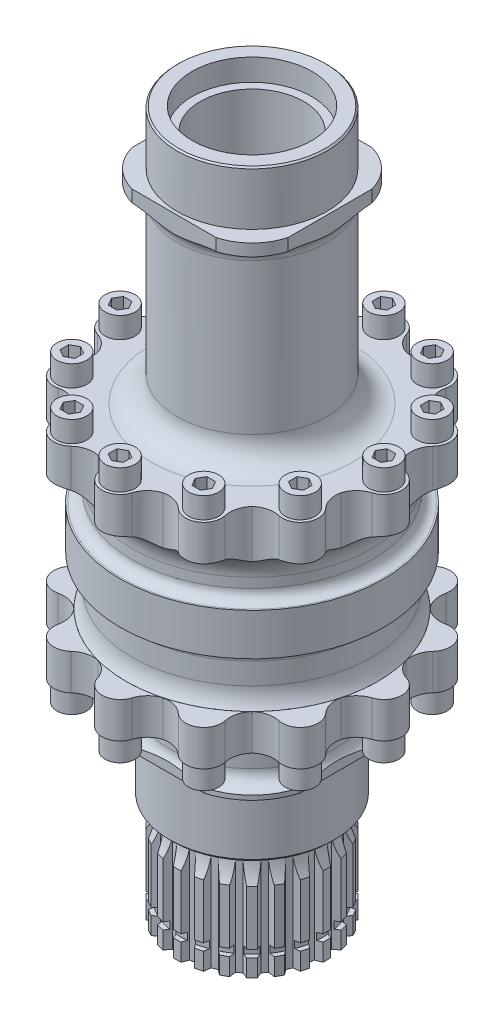
SolidWorks part; units mm, degrees
ref_plane "Front Plane" through (0, 0, 0) normal (0, 0, 1) x (1, 0, 0)
ref_plane "Top Plane" through (0, 0, 0) normal (0, 1, 0) x (1, 0, 0)
ref_plane "Right Plane" through (0, 0, 0) normal (1, 0, 0) x (0, 0, -1)
sketch "Sketch1" plane through (0, 0, 0) normal (0, 1, 0) x (1, 0, 0)
  circle A0 centre (0, 0) radius 44
  dimension "D1" = 88
extrude "Boss-Extrude1" add sketch "Sketch1" along normal mid plane 14
ref_plane "Plane1" through (0, 35.625, 0) normal (0, 1, 0) x (1, 0, 0)
sketch "Sketch2" plane through (0, 35.625, 0) normal (0, 1, 0) x (1, 0, 0)
  circle A0 centre (0, 0) radius 40
  dimension "D1" = 80
extrude "Boss-Extrude2" add sketch "Sketch2" against normal up to surface (42.625 mm away)
sketch "Sketch3" plane through (0, 35.625, 0) normal (0, 1, 0) x (1, 0, 0)
  circle A0 centre (0, 0) radius 42
  dimension "D1" = 84
extrude "Boss-Extrude3" add sketch "Sketch3" against normal blind 12
sketch "Sketch4" plane through (0, 35.625, 0) normal (0, 1, 0) x (1, 0, 0)
  line L0 (-11.2231, 40.4727) -> (11.2231, 40.4727)
  arc A1 (5.7261, 45.7922) -> (-5.7261, 45.7922) centre (0, 44) ccw
  circle A2 centre (0, 0) radius 42
  circle A3 centre (0, 0) radius 42
  arc A4 (-11.2231, 40.4727) -> (-5.7261, 45.7922) centre (-13.3609, 48.1818) ccw
  arc A5 (5.7261, 45.7922) -> (11.2231, 40.4727) centre (13.3609, 48.1818) ccw
  dimension "D2" = 12
  dimension "D4" = 16
  dimension "D5" = 16
  dimension "D3" = 44
  dimension "D1" = 0
extrude "Boss-Extrude4" add sketch "Sketch4" against normal up to surface (59.25 mm away) contours A1 A4 L0 A5
pattern_circular "CirPattern1" count 12 over 360 about axis through (0, 0, 0) along (0, 1, 0) of "Boss-Extrude4"
sketch "Sketch6" plane through (0, 35.625, 0) normal (0, 1, 0) x (1, 0, 0)
  circle A0 centre (0, 44) radius 5
  arc A1 (5.7261, 45.7922) -> (-5.7261, 45.7922) centre (0, 44) ccw construction
  dimension "D1" = 10
extrude "Boss-Extrude5" add sketch "Sketch6" along normal blind 7 separate body
sketch "Sketch7" plane through (0, 42.625, 0) normal (0, 1, 0) x (1, 0, 0)
  line L1 (2.5, 45.4434) -> (0, 46.8868)
  line L2 (0, 46.8868) -> (-2.5, 45.4434)
  line L3 (-2.5, 45.4434) -> (-2.5, 42.5566)
  line L4 (-2.5, 42.5566) -> (0, 41.1132)
  line L5 (0, 41.1132) -> (2.5, 42.5566)
  line L6 (2.5, 42.5566) -> (2.5, 45.4434)
  circle A0 centre (0, 44) radius 2.5 construction
  dimension "D1" = 5
extrude "Cut-Extrude1" cut sketch "Sketch7" against normal blind 4.5
pattern_circular "CirPattern5" count 12 over 360 about axis through (0, 0, 0) along (0, 1, 0) of bodies 118
mirror "Mirror2" about plane through (0, 0, 0) normal (0, 1, 0) of "Boss-Extrude2"
mirror "Mirror3" about plane through (0, 0, 0) normal (0, 1, 0) of "Boss-Extrude3"
sketch "Sketch8" plane through (0, -35.625, 0) normal (0, -1, 0) x (1, 0, 0)
  line L0 (40.5785, 10.873) -> (40.5785, -10.873)
  line L1 (40.5785, -10.873) -> (29.7055, -29.7055)
  line L2 (29.7055, -29.7055) -> (10.873, -40.5785)
  line L3 (10.873, -40.5785) -> (-10.873, -40.5785)
  line L4 (-10.873, -40.5785) -> (-29.7055, -29.7055)
  line L5 (-29.7055, -29.7055) -> (-40.5785, -10.873)
  line L6 (-40.5785, -10.873) -> (-40.5785, 10.873)
  line L7 (-40.5785, 10.873) -> (-29.7055, 29.7055)
  line L8 (-29.7055, 29.7055) -> (-10.873, 40.5785)
  line L9 (-10.873, 40.5785) -> (10.873, 40.5785)
  line L10 (10.873, 40.5785) -> (29.7055, 29.7055)
  line L11 (29.7055, 29.7055) -> (40.5785, 10.873)
  circle A2 centre (0, 0) radius 42
  circle A3 centre (0, 0) radius 42
  arc A10 (40.5785, -10.873) -> (42.5203, -17.9372) centre (48.4071, -12.5201) ccw
  arc A11 (36.7942, -27.855) -> (42.5203, -17.9372) centre (38.1051, -22) ccw
  arc A12 (36.7942, -27.855) -> (29.7055, -29.7055) centre (35.0463, -35.6617) ccw
  arc A13 (45.7922, -5.7261) -> (40.5785, -10.873) centre (48.1818, -13.3609) ccw
  arc A14 (40.5785, 10.873) -> (45.7922, 5.7261) centre (48.1818, 13.3609) ccw
  arc A15 (45.7922, -5.7261) -> (45.7922, 5.7261) centre (44, 0) ccw
  arc A16 (45.7922, -5.7261) -> (40.5785, -10.873) centre (48.1818, -13.3609) ccw
  arc A17 (40.5785, 10.873) -> (45.7922, 5.7261) centre (48.1818, 13.3609) ccw
  arc A18 (45.7922, -5.7261) -> (45.7922, 5.7261) centre (44, 0) ccw
  arc A19 (29.7055, -29.7055) -> (27.855, -36.7942) centre (35.6617, -35.0463) ccw
  arc A20 (17.9372, -42.5203) -> (27.855, -36.7942) centre (22, -38.1051) ccw
  arc A21 (17.9372, -42.5203) -> (10.873, -40.5785) centre (12.5201, -48.4071) ccw
  arc A22 (10.873, -40.5785) -> (5.7261, -45.7922) centre (13.3609, -48.1818) ccw
  arc A23 (-5.7261, -45.7922) -> (5.7261, -45.7922) centre (0, -44) ccw
  arc A24 (-5.7261, -45.7922) -> (-10.873, -40.5785) centre (-13.3609, -48.1818) ccw
  arc A25 (-10.873, -40.5785) -> (-17.9372, -42.5203) centre (-12.5201, -48.4071) ccw
  arc A26 (-27.855, -36.7942) -> (-17.9372, -42.5203) centre (-22, -38.1051) ccw
  arc A27 (-27.855, -36.7942) -> (-29.7055, -29.7055) centre (-35.6617, -35.0463) ccw
  arc A28 (-29.7055, -29.7055) -> (-36.7942, -27.855) centre (-35.0463, -35.6617) ccw
  arc A29 (-42.5203, -17.9372) -> (-36.7942, -27.855) centre (-38.1051, -22) ccw
  arc A30 (-42.5203, -17.9372) -> (-40.5785, -10.873) centre (-48.4071, -12.5201) ccw
  arc A31 (-40.5785, -10.873) -> (-45.7922, -5.7261) centre (-48.1818, -13.3609) ccw
  arc A32 (-45.7922, 5.7261) -> (-45.7922, -5.7261) centre (-44, 0) ccw
  arc A33 (-45.7922, 5.7261) -> (-40.5785, 10.873) centre (-48.1818, 13.3609) ccw
  arc A34 (-40.5785, 10.873) -> (-42.5203, 17.9372) centre (-48.4071, 12.5201) ccw
  arc A35 (-36.7942, 27.855) -> (-42.5203, 17.9372) centre (-38.1051, 22) ccw
  arc A36 (-36.7942, 27.855) -> (-29.7055, 29.7055) centre (-35.0463, 35.6617) ccw
  arc A37 (-29.7055, 29.7055) -> (-27.855, 36.7942) centre (-35.6617, 35.0463) ccw
  arc A38 (-17.9372, 42.5203) -> (-27.855, 36.7942) centre (-22, 38.1051) ccw
  arc A39 (-17.9372, 42.5203) -> (-10.873, 40.5785) centre (-12.5201, 48.4071) ccw
  arc A40 (-10.873, 40.5785) -> (-5.7261, 45.7922) centre (-13.3609, 48.1818) ccw
  arc A41 (5.7261, 45.7922) -> (-5.7261, 45.7922) centre (0, 44) ccw
  arc A42 (5.7261, 45.7922) -> (10.873, 40.5785) centre (13.3609, 48.1818) ccw
  arc A43 (10.873, 40.5785) -> (17.9372, 42.5203) centre (12.5201, 48.4071) ccw
  arc A44 (27.855, 36.7942) -> (17.9372, 42.5203) centre (22, 38.1051) ccw
  arc A45 (27.855, 36.7942) -> (29.7055, 29.7055) centre (35.6617, 35.0463) ccw
  arc A46 (29.7055, 29.7055) -> (36.7942, 27.855) centre (35.0463, 35.6617) ccw
  arc A47 (42.5203, 17.9372) -> (36.7942, 27.855) centre (38.1051, 22) ccw
  arc A48 (42.5203, 17.9372) -> (40.5785, 10.873) centre (48.4071, 12.5201) ccw
  point P90 (0, 0)
  circle M5 centre (0, 0) radius 42
  dimension "D1" = 0
  dimension "D2" = 0
  dimension "D3" = 12
extrude "Boss-Extrude10" add sketch "Sketch8" against normal up to surface (12 mm away) separate body contours A48 A47 A46 L11 M5
pattern_circular "CirPattern12" count 12 over 360 about axis through (0, 0, 0) along (0, 1, 0) of bodies 138
mirror "Mirror6" about plane through (0, 0, 0) normal (0, 1, 0) of bodies 120 121 122 123 124 125 126 127 128 129 130 118
sketch "Sketch9" plane through (0, 35.625, 0) normal (0, 1, 0) x (1, 0, 0)
  circle A0 centre (0, 0) radius 25
  dimension "D1" = 50
extrude "Boss-Extrude11" add sketch "Sketch9" along normal blind 86
sketch "Sketch10" plane through (0, 121.625, 0) normal (0, 1, 0) x (1, 0, 0)
  circle A0 centre (0, 0) radius 20
  dimension "D1" = 40
extrude "Cut-Extrude2" cut sketch "Sketch10" against normal blind 7.3
sketch "Sketch11" plane through (0, 114.325, 0) normal (0, 1, 0) x (1, 0, 0)
  circle A0 centre (0, 0) radius 17.25
  dimension "D1" = 34.5
extrude "Cut-Extrude3" cut sketch "Sketch11" against normal blind 108.55 from surface at 7.3 starting at face at (0, 121.625, 20)
ref_plane "Plane2" through (0, 103.625, 0) normal (0, 1, 0) x (1, 0, 0)
sketch "Sketch12" plane through (0, 103.625, 0) normal (0, 1, 0) x (1, 0, 0)
  line L1 (-14, 26) -> (14, 26)
  line L2 (-26, 14) -> (-26, -14)
  line L3 (-14, -26) -> (14, -26)
  line L4 (26, 14) -> (26, -14)
  arc A2 (14, 26) -> (26, 14) centre (9.5837, 9.5837) cw
  arc A3 (26, -14) -> (14, -26) centre (9.5837, -9.5837) cw
  arc A4 (-14, 26) -> (-26, 14) centre (-9.5837, 9.5837) ccw
  arc A5 (-14, -26) -> (-26, -14) centre (-9.5837, -9.5837) cw
  circle A6 centre (0, 0) radius 22.5
  point P0 (0, 0)
  point P1 (0, -26)
  point P3 (26, 0)
  dimension "D3" = 12
  dimension "D4" = 12
  dimension "D5" = 17
  dimension "D12" = 17
  dimension "D13" = 17
  dimension "D14" = 17
  dimension "D15" = 45
  dimension "D1" = 52
  dimension "D2" = 52
  dimension "D6" = 12
  dimension "D7" = 12
  dimension "D8" = 12
  dimension "D9" = 12
  dimension "D10" = 12
  dimension "D11" = 12
extrude "Boss-Extrude12" add sketch "Sketch12" against normal blind 4
fillet "Fillet1" radius 9.9 2 edges at (0, -23.625, -40) (0, 23.625, 40)
fillet "Fillet2" radius 3.5 2 edges at (0, 7, 40) (0, -7, 40)
fillet "Fillet3" radius 5 1 edges at (0, 99.625, -25)
chamfer "Chamfer1" distance 0.5 angle 45 1 edges at (0, 121.625, 25)
sketch "Sketch13" plane through (0, -35.625, 0) normal (0, -1, 0) x (1, 0, 0)
  circle A0 centre (0, 0) radius 27.5
  dimension "D1" = 55
extrude "Boss-Extrude13" add sketch "Sketch13" along normal blind 42
sketch "Sketch14" plane through (0, -77.625, 0) normal (0, -1, 0) x (1, 0, 0)
  circle A0 centre (0, 0) radius 23
  dimension "D1" = 46
extrude "Boss-Extrude14" add sketch "Sketch14" along normal blind 35
ref_plane "Plane3" through (0, -56.375, 0) normal (0, 1, 0) x (1, 0, 0)
sketch "Sketch15" plane through (0, -56.375, 0) normal (0, 1, 0) x (1, 0, 0)
  line L0 (-12.5, 28.5) -> (12.5, 28.5)
  line L2 (-28.5, 12.5) -> (-28.5, -12.5)
  line L3 (-12.5, -28.5) -> (12.5, -28.5)
  line L4 (28.5, 12.5) -> (28.5, -12.5)
  arc A0 (-28.5, -12.5) -> (-12.5, -28.5) centre (-6.3402, -6.3402) ccw
  arc A1 (-12.5, 28.5) -> (-28.5, 12.5) centre (-6.3402, 6.3402) ccw
  arc A2 (28.5, 12.5) -> (12.5, 28.5) centre (6.3402, 6.3402) ccw
  arc A3 (12.5, -28.5) -> (28.5, -12.5) centre (6.3402, -6.3402) ccw
  point P0 (0, 0)
  point P21 (0, 0)
  dimension "D5" = 23
  dimension "D1" = 57
  dimension "D3" = 16
  dimension "D4" = 16
  dimension "D6" = 4
extrude "Boss-Extrude15" add sketch "Sketch15" along normal blind 1.5
fillet "Fillet4" radius 4.465 1 edges at (0, -54.875, 27.5)
fillet "Fillet5" radius 8.75 1 edges at (0, 35.625, 25)
fillet "Fillet6" radius 8.75 1 edges at (0, -35.625, -27.5)
chamfer "Chamfer2" distance 1 angle 45 1 edges at (0, -77.625, -27.5)
sketch "Sketch16" plane through (0, -112.625, 0) normal (0, -1, 0) x (1, 0, 0)
  circle A0 centre (0, 0) radius 20
  dimension "D1" = 40
extrude "Cut-Extrude4" cut sketch "Sketch16" against normal blind 7
sketch "Sketch17" plane through (0, -105.625, 0) normal (0, -1, 0) x (1, 0, 0)
  circle A0 centre (0, 0) radius 17.5
  dimension "D1" = 35
extrude "Cut-Extrude5" cut sketch "Sketch17" against normal blind 97.35 from surface at 7 starting at face at (0, -112.625, -20)
sketch "Sketch18" plane through (0, -112.625, 0) normal (0, -1, 0) x (1, 0, 0)
  line L0 (0, 0) -> (0, 50000) construction
  line L1 (1.25, 25) -> (-1.25, 25)
  line L2 (-1.25, 25) -> (-2.1, 22.9039)
  line L3 (1.25, 25) -> (2.1, 22.9039)
  line L4 (-2.1, 22.9039) -> (2.1, 22.9039)
  circle A2 centre (0, 0) radius 23
  circle A3 centre (0, 0) radius 23 construction
  point P10 (0, 25)
  dimension "D2" = 2.5
  dimension "D3" = 4.2
  dimension "D4" = 25
  dimension "D1" = 0
extrude "Boss-Extrude16" add sketch "Sketch18" against normal up to surface (35 mm away) up to face at (0, -77.625, -26.5)
pattern_circular "CirPattern13" count 24 over 360 about axis through (0, 0, 0) along (0, 1, 0) of "Boss-Extrude16"
sketch "Sketch19" plane through (0, 0, 0) normal (1, 0, 0) x (0, 0, -1)
  line L0 (-50.0396, -105.625) -> (49949.9604, -105.625) construction
  line L1 (-29.1243, -77.625) -> (-22.8, -77.625)
  line L2 (-23.5, -104.425) -> (-29.7038, -104.425)
  line L3 (-23.5, -104.425) -> (-23.5, -106.825)
  line L4 (-23.5, -106.825) -> (-29.7038, -106.825)
  line L5 (-29.7038, -104.425) -> (-29.7038, -106.825)
  line L6 (-23.5, -104.425) -> (-29.7038, -106.825) construction
  line L7 (-23.5, -106.825) -> (-29.7038, -104.425) construction
  line L8 (-25, -112.625) -> (-20, -112.625)
  line L9 (20, -112.625) -> (25, -112.625)
  line L10 (20, -112.625) -> (25, -112.625)
  line L11 (-25, -112.625) -> (-20, -112.625)
  line L12 (-25, -77.625) -> (-25, -112.625)
  line L13 (-25, -77.625) -> (-25, -112.625)
  line L14 (-29.1243, -77.625) -> (-25, -86.225)
  line L15 (-22.8, -77.625) -> (-22.8, 49922.375) construction
  arc A0 (-22.8, -77.625) -> (-25, -86.225) centre (-40.7091, -77.625) cw
  point P2 (-26.6019, -105.625)
  dimension "D1" = 7
  dimension "D2" = 2.4
  dimension "D3" = 23.5
  dimension "D4" = 6.2038
  dimension "D5" = 22.8
  dimension "D6" = 8.6
  dimension "D7" = 6.3243
ref_axis "Axis1" through (0, -15.275, 0) along (0, -1, 0)
revolve "Cut-Revolve1" cut sketch "Sketch19" angle 360 about axis through (0, -15.275, 0) along (0, -1, 0)
ref_plane "Plane4" through (0, 4.5, 0) normal (0, -1, 0) x (-1, 0, 0)
